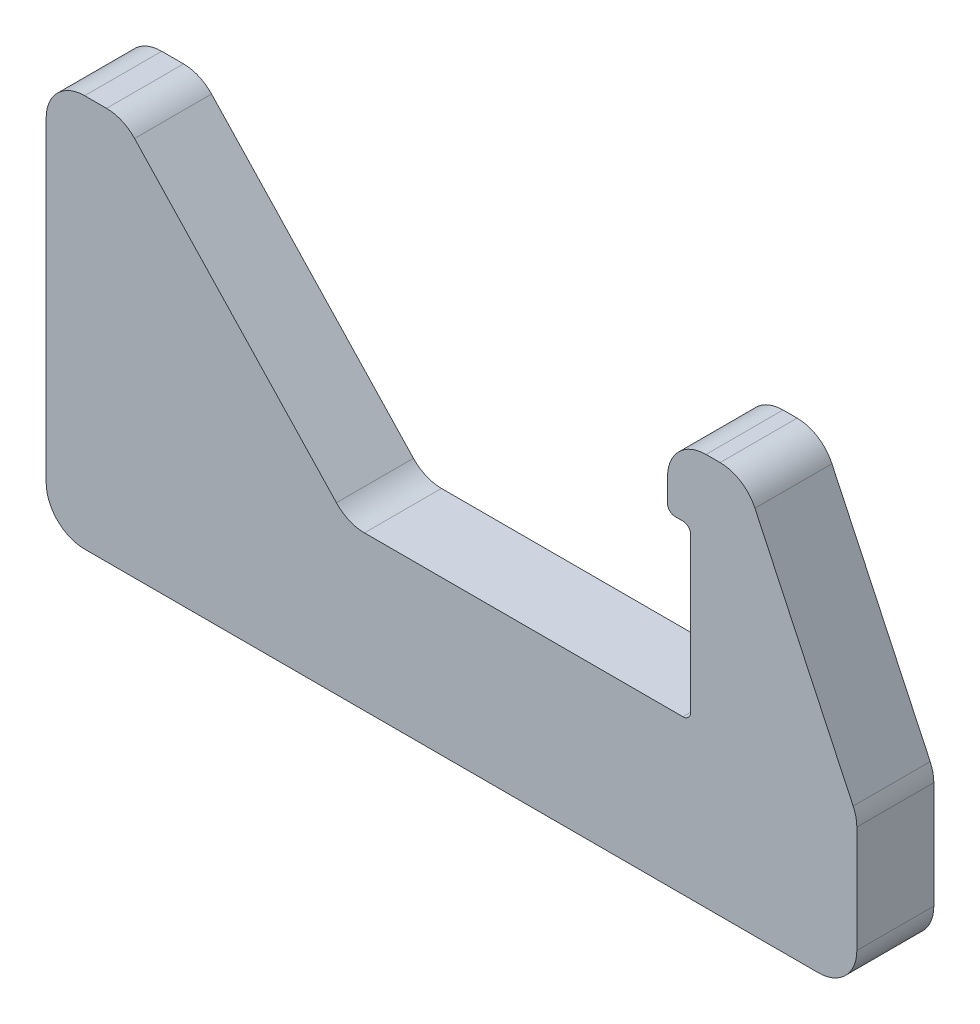
SolidWorks part; units mm, degrees
ref_plane "Front Plane" through (0, 0, 0) normal (0, 0, 1) x (1, 0, 0)
ref_plane "Top Plane" through (0, 0, 0) normal (0, 1, 0) x (1, 0, 0)
ref_plane "Right Plane" through (0, 0, 0) normal (1, 0, 0) x (0, 0, -1)
sketch "Sketch1" plane through (0, 0, 0) normal (0, 0, 1) x (1, 0, 0)
  line L0 (-105.2726, 0) -> (-105.2726, 51)
  line L1 (-105.2726, 51) -> (-95.2726, 51)
  line L2 (-95.2726, 51) -> (-66.1016, 20)
  line L3 (-66.1016, 20) -> (-21.5831, 20)
  line L4 (-21.5831, 20) -> (-21.5831, 42)
  line L5 (-21.5831, 42) -> (-24.5831, 42)
  line L6 (-24.5831, 42) -> (-24.5831, 51)
  line L7 (-24.5831, 51) -> (-14.5831, 51)
  line L8 (-14.5831, 51) -> (0, 20)
  line L9 (0, 20) -> (0, 0)
  line L10 (0, 0) -> (-105.2726, 0)
  point P3 (103.5728, 51)
  point P13 (171.1509, 20)
  point P14 (172.3042, 0)
  point P15 (28.0097, 20)
  point P16 (122.3178, 20)
  point P17 (74.9955, 20)
  point P18 (35.8257, 22.0818)
  point P19 (24.0375, 26.8374)
  point P20 (34.1243, 20)
  point P21 (10, 51)
  point P22 (22.4842, 20)
  point P23 (0, 0)
  point P24 (1.3919, 0)
  point P25 (0, 0)
  point P27 (-67.5265, 20)
  point P28 (-58.6473, 20)
  point P29 (-73.411, 20)
  point P30 (-66.1016, 20)
  dimension "D2" = 10
  dimension "D3" = 9
  dimension "D4" = 3
  dimension "D5" = 22
  dimension "D6" = 20
  dimension "D7" = 10
extrude "Boss-Extrude1" add sketch "Sketch1" along normal blind 10
fillet "Fillet1" radius 5 8 edges at (0, 0, 5) (-105.2726, 0, 5) (-105.2726, 51, 5) (-95.2726, 51, 5) (-66.1016, 20, 5) (0, 20, 5) (-14.5831, 51, 5) (-24.5831, 51, 5)
fillet "Fillet2" radius 1 3 edges at (-21.5831, 20, 5) (-21.5831, 42, 5) (-24.5831, 42, 5)
